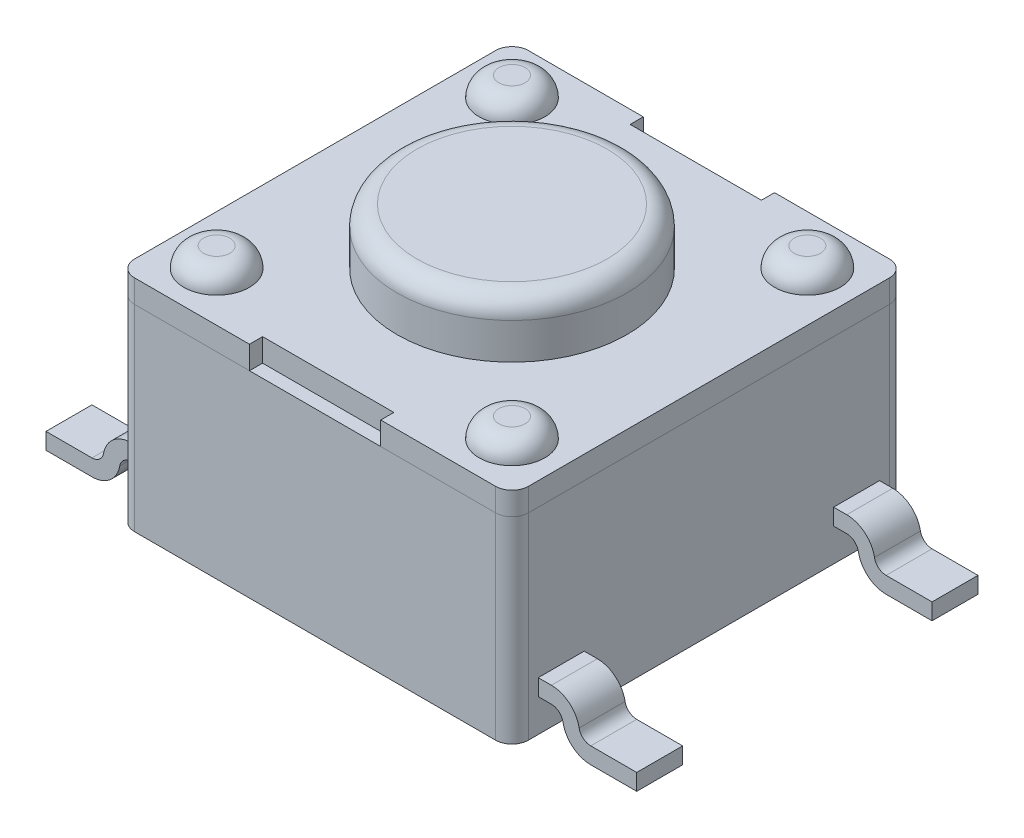
SolidWorks part; units mm, degrees
ref_plane "Front Plane" through (0, 0, 0) normal (0, 0, 1) x (1, 0, 0)
ref_plane "Top Plane" through (0, 0, 0) normal (0, 1, 0) x (1, 0, 0)
ref_plane "Right Plane" through (0, 0, 0) normal (1, 0, 0) x (0, 0, -1)
sketch "Sketch1" plane through (0, 0, 0) normal (0, 1, 0) x (1, 0, 0)
  line L1 (3, -3) -> (-3, -3)
  line L2 (3, -3) -> (3, 3)
  line L3 (3, 3) -> (-3, 3)
  line L4 (-3, -3) -> (-3, 3)
  line L5 (3, -3) -> (-3, 3) construction
  line L6 (3, 3) -> (-3, -3) construction
  point P0 (0, 0)
  dimension "D1" = 6
extrude "Boss-Extrude1" add sketch "Sketch1" along normal blind 3
sketch "Sketch4" plane through (0, 3, 0) normal (0, 1, 0) x (1, 0, 0)
  line L0 (-1, -3) -> (-1, -2.8)
  line L1 (3, -3) -> (-3, -3)
  line L2 (3, -3) -> (3, 3)
  line L3 (3, 3) -> (-3, 3)
  line L4 (-3, -3) -> (-3, 3)
  line L5 (3, -3) -> (-3, 3) construction
  line L6 (3, 3) -> (-3, -3) construction
  line L7 (-1, -2.8) -> (1, -2.8)
  line L8 (1, -2.8) -> (1, -3)
  line L9 (-1, 3) -> (-1, 2.8)
  line L10 (-1, 2.8) -> (1, 2.8)
  line L11 (1, 2.8) -> (1, 3)
  point P0 (0, 0)
  point P13 (0, -2.8)
  line M9 (-3, 3) -> (-3, -3)
  line M10 (-3, -3) -> (3, -3)
  line M11 (3, -3) -> (3, 3)
  line M12 (3, 3) -> (-3, 3)
  dimension "D1" = 0.2
  dimension "D2" = 2
extrude "Boss-Extrude4" add sketch "Sketch4" along normal blind 0.35 separate body contours L11 L10 L9 L3 L0 L7 L8 L1 M9 M10 M11 M12 region at (0, 3, 0)
sketch "Sketch2" plane through (0, 3.35, 0) normal (0, 1, 0) x (1, 0, 0)
  circle A0 centre (0, 0) radius 1.75
  dimension "D1" = 3.5
extrude "Boss-Extrude2" add sketch "Sketch2" along normal blind 0.85
sketch "Sketch3" plane through (0, 3.35, 0) normal (0, 1, 0) x (1, 0, 0)
  line L1 (2.25, -2.25) -> (-2.25, -2.25) construction
  line L2 (2.25, -2.25) -> (2.25, 2.25) construction
  line L3 (2.25, 2.25) -> (-2.25, 2.25) construction
  line L4 (-2.25, -2.25) -> (-2.25, 2.25) construction
  line L5 (2.25, -2.25) -> (-2.25, 2.25) construction
  line L6 (2.25, 2.25) -> (-2.25, -2.25) construction
  circle A0 centre (2.25, -2.25) radius 0.5
  circle A1 centre (2.25, 2.25) radius 0.5
  circle A2 centre (-2.25, 2.25) radius 0.5
  circle A3 centre (-2.25, -2.25) radius 0.5
  point P0 (0, 0)
  dimension "D2" = 1
  dimension "D1" = 4.5
extrude "Boss-Extrude3" add sketch "Sketch3" along normal blind 0.3
sketch "Sketch5" plane through (0, 0, 3) normal (0, 0, 1) x (1, 0, 0)
  line L0 (3, 0.75) -> (3.2, 0.75)
  line L1 (3, 3) -> (3, 0) construction
  line L2 (3.8, 0.25) -> (4.5, 0.25)
  line L3 (4.5, 0.25) -> (4.5, 0)
  line L4 (4.5, 0) -> (3.8, 0)
  line L5 (3.2, 0.5) -> (3, 0.5)
  line L6 (3, 0.5) -> (3, 0.75)
  line L7 (-3, 0) -> (3, 0) construction
  line L8 (0, 0) -> (0, 3) construction
  line L9 (-3, 3) -> (3, 3) construction
  line L10 (-3.2, 0.5) -> (-3, 0.5)
  line L11 (-4.5, 0) -> (-3.8, 0)
  line L12 (-4.5, 0.25) -> (-4.5, 0)
  line L13 (-3.8, 0.25) -> (-4.5, 0.25)
  line L14 (-3, 0.75) -> (-3.2, 0.75)
  line L15 (-3, 0.5) -> (-3, 0.75)
  arc A0 (3.2, 0.75) -> (3.623, 0.3975) centre (3.2, 0.32) cw
  arc A1 (3.623, 0.3975) -> (3.8, 0.25) centre (3.8, 0.43) ccw
  arc A2 (3.8, 0) -> (3.377, 0.3525) centre (3.8, 0.43) cw
  arc A3 (3.377, 0.3525) -> (3.2, 0.5) centre (3.2, 0.32) ccw
  arc A4 (-3.377, 0.3525) -> (-3.2, 0.5) centre (-3.2, 0.32) cw
  arc A5 (-3.8, 0) -> (-3.377, 0.3525) centre (-3.8, 0.43) ccw
  arc A6 (-3.623, 0.3975) -> (-3.8, 0.25) centre (-3.8, 0.43) cw
  arc A7 (-3.2, 0.75) -> (-3.623, 0.3975) centre (-3.2, 0.32) ccw
  point P31 (3.3152, 0.4583)
  dimension "D1" = 0.25
  dimension "D2" = 0.7
  dimension "D3" = 4.5
  dimension "D4" = 0.2
  dimension "D5" = 0.5
extrude "Boss-Extrude5" add sketch "Sketch5" against normal blind 0.7 from offset 0.4 offset against normal yes
pattern_linear "LPattern1" count 2 spacing 4.5 along (0, 0, -1) of "Boss-Extrude5"
fillet "Fillet1" radius 0.25 4 edges at (-3, 1.5, -3) (3, 1.5, -3) (-3, 1.5, 3) (3, 1.5, 3)
fillet "Fillet2" radius 0.25 4 edges at (-3, 3.175, 3) (3, 3.175, 3) (-3, 3.175, -3) (3, 3.175, -3)
fillet "Fillet3" radius 0.3 1 edges at (2.25, 3.65, 2.75)
fillet "Fillet4" radius 0.3 1 edges at (-2.25, 3.65, 2.75)
fillet "Fillet5" radius 0.3 1 edges at (-2.25, 3.65, -1.75)
fillet "Fillet6" radius 0.3 1 edges at (2.25, 3.65, -1.75)
fillet "Fillet7" radius 0.3 1 edges at (0, 4.2, 1.75)
